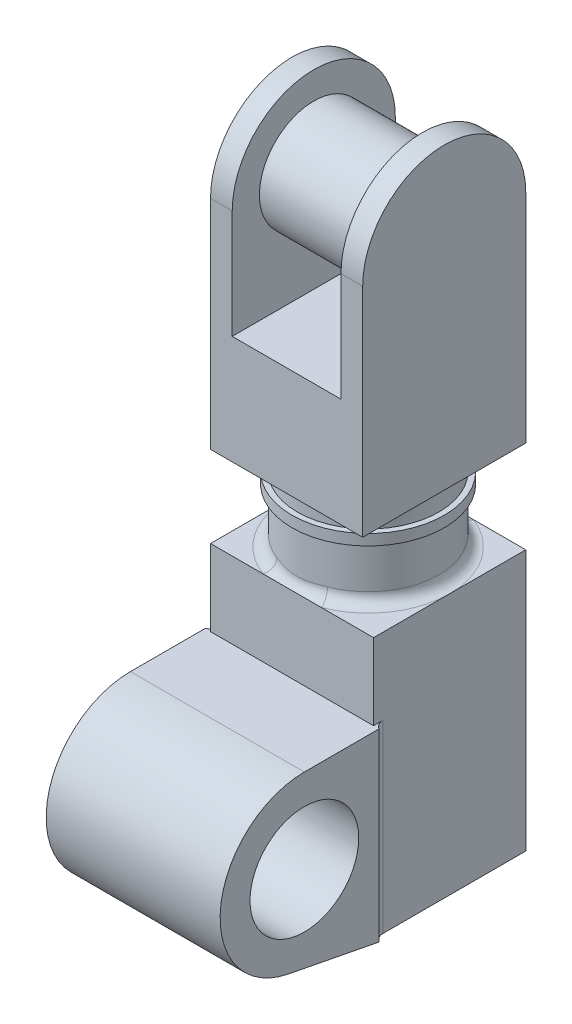
SolidWorks part; units mm, degrees
ref_plane "Ön Düzlem" through (0, 0, 0) normal (0, 0, 1) x (1, 0, 0)
ref_plane "Üst Düzlem" through (0, 0, 0) normal (0, 1, 0) x (1, 0, 0)
ref_plane "Sağ Düzlem" through (0, 0, 0) normal (1, 0, 0) x (0, 0, -1)
sketch "Çizim2" plane through (0, 0, 0) normal (0, 1, 0) x (1, 0, 0)
  line L1 (-75, -70) -> (75, -70)
  line L2 (-75, -70) -> (-75, 70)
  line L3 (-75, 70) -> (75, 70)
  line L4 (75, -70) -> (75, 70)
  line L5 (-75, -70) -> (75, 70) construction
  line L6 (-75, 70) -> (75, -70) construction
  point P0 (0, 0)
  dimension "D1" = 150
  dimension "D2" = 140
extrude "Yükseklik-Ekstrüzyon1" add sketch "Çizim2" along normal blind 240
sketch "Çizim3" plane through (0, 240, 0) normal (0, 1, 0) x (1, 0, 0)
  circle A0 centre (0, 0) radius 65
  dimension "D1" = 130
extrude "Yükseklik-Ekstrüzyon2" add sketch "Çizim3" along normal blind 50
sketch "Çizim4" plane through (0, 290, 0) normal (0, 1, 0) x (1, 0, 0)
  circle A0 centre (0, 0) radius 70
  dimension "D1" = 140
extrude "Yükseklik-Ekstrüzyon3" add sketch "Çizim4" along normal blind 10
sketch "Çizim5" plane through (0, 0, 0) normal (1, 0, 0) x (0, 0, -1)
  line L0 (-70, 0) -> (-153.4383, 16.2188)
  line L1 (70, 0) -> (-70, 0) construction
  line L2 (-138.6506, 169.7949) -> (-70, 169.7949)
  line L3 (-70, 240) -> (-70, 0) construction
  line L4 (-70, 0) -> (-70, 169.7949)
  arc A0 (-138.6506, 169.7949) -> (-153.4383, 16.2188) centre (-138.6506, 92.2949) ccw
  circle A1 centre (-138.6506, 92.2949) radius 50
  dimension "D1" = 155
  dimension "D2" = 100
  dimension "D3" = 191
  dimension "D4" = 85
extrude "Yükseklik-Ekstrüzyon4" add sketch "Çizim5" along normal mid plane 160
fillet "Radyus1" radius 10 3 edges at (-75, 84.8974, 70) (75, 84.8974, 70) (0, 240, 65)
sketch "Çizim6" plane through (0, 300, 0) normal (0, 1, 0) x (1, 0, 0)
  circle A0 centre (0, 0) radius 65
  dimension "D1" = 130
extrude "Yükseklik-Ekstrüzyon5" add sketch "Çizim6" along normal blind 20
sketch "Çizim7" plane through (0, 0, 0) normal (1, 0, 0) x (0, 0, -1)
  line L0 (-75, 520) -> (-75, 320)
  line L1 (75, 520) -> (75, 320)
  line L2 (75, 320) -> (-75, 320)
  line L3 (65, 320) -> (-65, 320) construction
  line L4 (65, 320) -> (-65, 320)
  arc A0 (75, 520) -> (-75, 520) centre (0, 520) ccw
  dimension "D1" = 150
  dimension "D2" = 200
  dimension "D3" = 520
extrude "Yükseklik-Ekstrüzyon6" add sketch "Çizim7" along normal mid plane 140 contours L1 A0 L0 L2 region at (0, 449.9936, 0)
sketch "Çizim8" plane through (0, 0, 0) normal (1, 0, 0) x (0, 0, -1)
  line L0 (-75, 520) -> (-75, 420)
  line L1 (-75, 520) -> (-75, 320) construction
  line L2 (-75, 420) -> (75, 420)
  line L3 (75, 520) -> (75, 320) construction
  line L4 (75, 420) -> (75, 520)
  arc A0 (75, 520) -> (-75, 520) centre (0, 520) ccw construction
  arc A1 (75, 520) -> (-75, 520) centre (0, 520) ccw
extrude "Kes-Ekstrüzyon1" cut sketch "Çizim8" against normal mid plane 100
sketch "Çizim9" plane through (50, 0, 0) normal (-1, 0, 0) x (0, 0, 1)
  circle A0 centre (0, 520) radius 50
  dimension "D1" = 100
extrude "Yükseklik-Ekstrüzyon7" add sketch "Çizim9" along normal up to next
